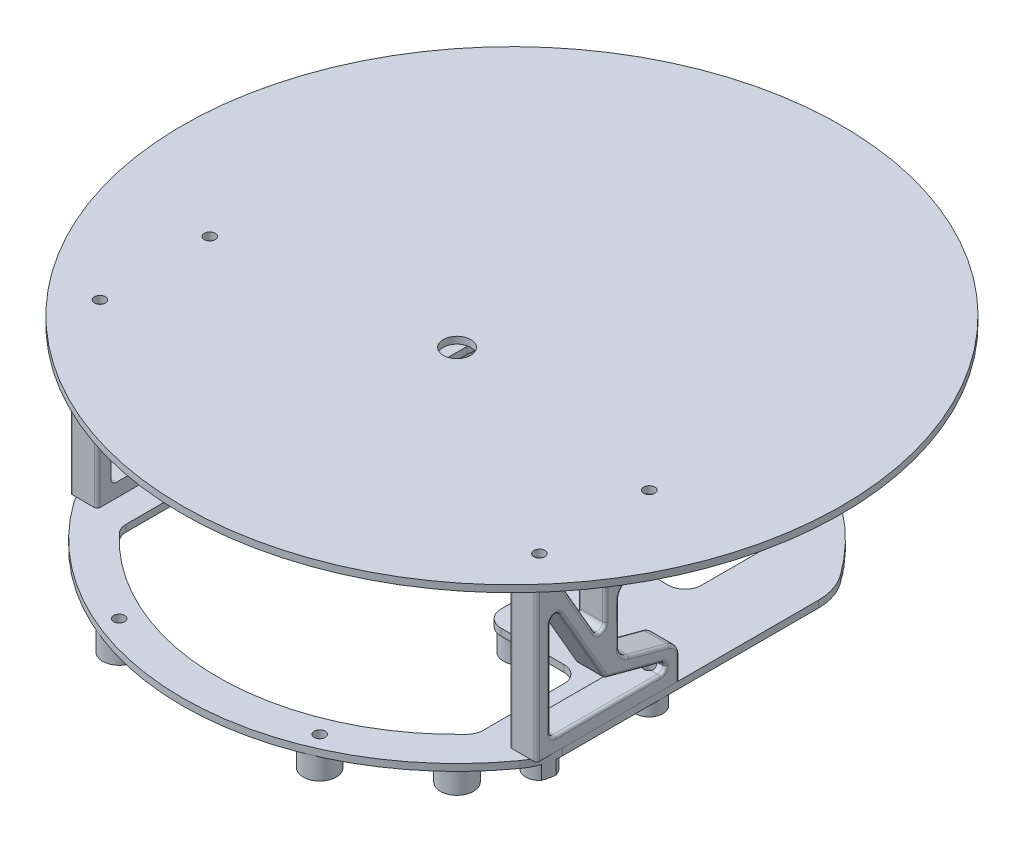
SolidWorks part; units mm, degrees
ref_plane "Front" through (0, 0, 0) normal (0, 0, 1) x (1, 0, 0)
ref_plane "Top" through (0, 0, 0) normal (0, 1, 0) x (1, 0, 0)
ref_plane "Right" through (0, 0, 0) normal (1, 0, 0) x (0, 0, -1)
sketch "Sketch1" plane through (0, 0, 0) normal (0, 1, 0) x (1, 0, 0)
  line L0 (0, 71.1393) -> (0, -87.7098) construction
  line L1 (-42.5, 26.3391) -> (-42.5, -26.3391)
  line L2 (42.5, 26.3391) -> (42.5, -26.3391)
  arc A0 (-42.5, -26.3391) -> (42.5, -26.3391) centre (0, 0) ccw
  arc A1 (42.5, 26.3391) -> (-42.5, 26.3391) centre (0, 0) ccw
  dimension "D1" = 100
  dimension "D2" = 85
extrude "Boss-Extrude1" add sketch "Sketch1" along normal blind 1.25
sketch "Sketch2" plane through (0, 0, 0) normal (0, -1, 0) x (1, 0, 0)
  line L0 (0, 45.5144) -> (0, -63.1722) construction
  line L1 (-51.2989, 0) -> (55.2567, 0) construction
  circle A0 centre (-33, 33) radius 3
  circle A2 centre (-33, 33) radius 1.125
  circle A4 centre (-33, -33) radius 1.125
  circle A5 centre (-33, -33) radius 3
  circle A6 centre (33, -33) radius 3
  circle A7 centre (33, -33) radius 1.125
  circle A8 centre (33, 33) radius 1.125
  circle A9 centre (33, 33) radius 3
  dimension "D3" = 2.25
  dimension "D4" = 6
  dimension "D1" = 66
  dimension "D2" = 66
extrude "Boss-Extrude2" add sketch "Sketch2" along normal blind 4
fillet "Fillet1" radius 10 4 edges at (-42.5, 0.625, -26.3391) (-42.5, 0.625, 26.3391) (42.5, 0.625, -26.3391) (42.5, 0.625, 26.3391)
sketch "Sketch3" plane through (0, 1.25, 0) normal (0, 1, 0) x (1, 0, 0)
  line L0 (0, 58.0627) -> (0, -62.1815) construction
  line L1 (-18.25, -6.75) -> (18.25, -6.75) construction
  line L2 (-18.25, -6.75) -> (-18.25, -43.25) construction
  line L3 (-18.25, -43.25) -> (18.25, -43.25) construction
  line L4 (18.25, -6.75) -> (18.25, -43.25) construction
  line L5 (-18.25, -6.75) -> (18.25, -43.25) construction
  line L6 (-18.25, -43.25) -> (18.25, -6.75) construction
  circle A0 centre (-18.25, -6.75) radius 1
  circle A1 centre (18.25, -6.75) radius 1
  circle A2 centre (18.25, -43.25) radius 1
  circle A3 centre (-18.25, -43.25) radius 1
  circle A4 centre (-40, -5) radius 1
  circle A5 centre (-40, -25) radius 1
  circle A6 centre (40, -25) radius 1
  circle A7 centre (40, -5) radius 1
  point P0 (0, -25)
  dimension "D1" = 2
  dimension "D2" = 36.5
  dimension "D3" = 25
  dimension "D4" = 20
  dimension "D5" = 80
  dimension "D6" = 0
sketch "Sketch4" plane through (0, 0, 0) normal (0, -1, 0) x (1, 0, 0)
  circle A0 centre (-18.25, 43.25) radius 3
  circle A1 centre (18.25, 43.25) radius 3
  circle A2 centre (18.25, 6.75) radius 3
  circle A3 centre (-18.25, 6.75) radius 3
  circle A4 centre (-40, 25) radius 2.5
  circle A5 centre (-40, 5) radius 2.5
  circle A6 centre (40, 25) radius 2.5
  circle A7 centre (40, 5) radius 2.5
  arc M10 (42.5, 23.3184) -> (40.625, 29.1481) centre (32.5, 23.3184) ccw
  arc M16 (-40.625, 29.1481) -> (-42.5, 23.3184) centre (-32.5, 23.3184) ccw
  dimension "D1" = 6
  dimension "D2" = 5
extrude "Boss-Extrude3" add sketch "Sketch4" along normal up to surface (4 mm away) contours A3 | A0 | A1 | A2 region at (-18.25, 0, 43.25) region at (18.25, 0, 43.25) region at (18.25, 0, 6.75) region at (-18.25, 0, 6.75) up to face at (-33, -4, 30)
extrude "Boss-Extrude7" add sketch "Sketch4<3>" along normal offset from surface (2.5 mm away) 1.5 contours A4 M16 | A6 M10 | A5 | A7 region at (-39.9675, 0, 24.9927) region at (39.9675, 0, 24.9927) up to face at (18.25, -4, 3.75)
sketch "Sketch4<3>" plane through (0, 0, 0) normal (0, -1, 0) x (1, 0, 0) same geometry as "Sketch4"
extrude "Cut-Extrude1" cut sketch "Sketch3" against normal through all
sketch "Sketch6" plane through (0, 0, 0) normal (0, -1, 0) x (1, 0, 0)
  line L0 (-29.5, -32.6458) -> (-29.5, -12)
  line L1 (-29.5, -12) -> (-6, -12)
  line L2 (29.5, -12) -> (29.5, -32.6458)
  line L3 (0, 0) -> (0, -57.2909) construction
  line L4 (-32.5, 28.9137) -> (-32.5, 10)
  line L5 (-32.5, 10) -> (-15, 10)
  line L6 (32.5, 10) -> (32.5, 28.9137)
  line L7 (-6, -12) -> (-6, -43.589)
  line L8 (6, -12) -> (6, -43.589)
  line L9 (6, -12) -> (29.5, -12)
  line L10 (15, 10) -> (32.5, 10)
  line L12 (-15, 10) -> (-15, 2)
  line L13 (-15, 2) -> (15, 2)
  line L14 (15, 10) -> (15, 2)
  arc A0 (-29.5, -32.6458) -> (-6, -43.589) centre (0, 0) ccw
  arc A1 (-40.625, -29.1481) -> (40.625, -29.1481) centre (0, 0) ccw construction
  arc A2 (-32.5, 28.9137) -> (32.5, 28.9137) centre (0, 0) cw
  arc A3 (40.625, 29.1481) -> (-40.625, 29.1481) centre (0, 0) ccw construction
  arc A4 (6, -43.589) -> (29.5, -32.6458) centre (0, 0) ccw
  dimension "D2" = 6
  dimension "D4" = 6.5
  dimension "D1" = 59
  dimension "D3" = 12
  dimension "D5" = 10
  dimension "D6" = 12
  dimension "D7" = 65
  dimension "D8" = 8
  dimension "D9" = 30
extrude "Cut-Extrude2" cut sketch "Sketch6" against normal through all
fillet "Fillet2" radius 3 16 edges at (-29.5, 0.625, -12) (-6, 0.625, -12) (-6, 0.625, -43.589) (29.5, 0.625, -12) (29.5, 0.625, -32.6458) (6, 0.625, -43.589) (6, 0.625, -12) (-29.5, 0.625, -32.6458) (32.5, 0.625, 28.9137) (-32.5, 0.625, 28.9137) (-32.5, 0.625, 10) (32.5, 0.625, 10) (15, 0.625, 2) (15, 0.625, 10) (-15, 0.625, 2) (-15, 0.625, 10)
ref_point "Point1"
ref_plane "Plane1" through (-40, 0, 0) normal (-1, 0, 0) x (0, 0, 1)
sketch "Sketch7" plane through (-40, 0, 0) normal (-1, 0, 0) x (0, 0, 1)
  line L0 (2, 1.25) -> (2, 7.25)
  line L1 (-23.3184, 1.25) -> (23.3184, 1.25) construction
  line L2 (2, 7.25) -> (13, 10.1974)
  line L3 (13, 10.1974) -> (13, 21.3026)
  line L4 (13, 21.3026) -> (2, 24.25)
  line L5 (2, 24.25) -> (2, 30.25)
  line L6 (2, 30.25) -> (28, 30.25)
  line L7 (28, 30.25) -> (28, 1.25)
  line L8 (28, 1.25) -> (2, 1.25)
  line L9 (4.5, 27.75) -> (23.8548, 27.75)
  line L11 (25.5, 3.75) -> (4.5, 3.75)
  line L12 (4.5, 3.75) -> (4.5, 5.3317)
  line L13 (4.5, 5.3317) -> (15.5, 8.2791)
  line L14 (15.5, 13.2791) -> (15.5, 23.2209)
  line L15 (15.5, 23.2209) -> (4.5, 26.1683)
  line L16 (4.5, 26.1683) -> (4.5, 27.75)
  line L17 (15.5, 8.2791) -> (25.5, 25.5996)
  line L19 (23.8548, 27.75) -> (15.5, 13.2791)
  line L21 (15.5, 8.2791) -> (15.5, 23.2209) construction
  line L22 (25.5, 25.5996) -> (25.5, 3.75)
  line L23 (25.5, 27.75) -> (25.5, 3.75) construction
  line L24 (4.5, 27.75) -> (25.5, 27.75) construction
  dimension "D1" = 2
  dimension "D2" = 26
  dimension "D3" = 15
  dimension "D4" = 15
  dimension "D5" = 15
  dimension "D6" = 6
  dimension "D7" = 29
  dimension "D9" = 2.5
  dimension "D10" = 30
  dimension "D8" = 2.5
extrude "Boss-Extrude4" add sketch "Sketch7" along normal mid plane 5 separate body
fillet "Fillet3" radius 2.5 4 edges at (-40, 7.25, 2) (-40, 10.1974, 13) (-40, 21.3026, 13) (-40, 24.25, 2)
fillet "Fillet4" radius 1 10 edges at (-40, 25.5996, 25.5) (-40, 8.2791, 15.5) (-40, 5.3317, 4.5) (-40, 3.75, 25.5) (-40, 3.75, 4.5) (-40, 13.2791, 15.5) (-40, 27.75, 4.5) (-40, 26.1683, 4.5) (-40, 23.2209, 15.5) (-40, 27.75, 23.8548)
fillet "Fillet5" radius 0.5 47 edges at (-37.5, 15.75, 28) (-37.5, 3.2908, 2) (-37.5, 6.8536, 2.5166) (-37.5, 8.7237, 7.5) (-37.5, 10.5939, 12.4834) (-37.5, 15.75, 13) (-37.5, 20.9061, 12.4834) (-37.5, 22.7763, 7.5) (-37.5, 24.6464, 2.5166) (-37.5, 28.2092, 2) (-42.5, 3.2908, 2) (-42.5, 6.8536, 2.5166) (-42.5, 8.7237, 7.5) (-42.5, 10.5939, 12.4834) (-42.5, 15.75, 13) (-42.5, 20.9061, 12.4834) (-42.5, 22.7763, 7.5) (-42.5, 24.6464, 2.5166) (-42.5, 28.2092, 2) (-42.5, 15.75, 28) (-42.5, 4.0108, 4.8265) (-42.5, 5.2093, 4.7358) (-42.5, 6.8511, 10.1705) (-42.5, 8.3445, 15.4498) (-42.5, 15.5027, 19.6705) (-42.5, 22.8335, 24.7588) (-42.5, 13.3088, 25.5) (-42.5, 4.0429, 25.2071) (-42.5, 3.75, 15) (-37.5, 27.4892, 4.8265) (-42.5, 27.4892, 4.8265) (-37.5, 26.2907, 4.7358) (-37.5, 24.6946, 10) (-37.5, 23.0623, 15.2934) (-37.5, 19.7324, 15.5) (-37.5, 16.0452, 16.2412) (-42.5, 26.2907, 4.7358) (-42.5, 24.6946, 10) (-42.5, 23.0623, 15.2934) (-42.5, 19.7324, 15.5) (-42.5, 16.0452, 16.2412) (-37.5, 27.75, 13.8114) (-42.5, 27.75, 13.8114) (-37.5, 21.3806, 20.1774) (-42.5, 21.3806, 20.1774) (-37.5, 27.25, 22.9887) (-42.5, 27.25, 22.9887)
sketch "Sketch8" plane through (0, 1.25, 0) normal (0, -1, 0) x (1, 0, 0)
  circle A2 centre (-40, 5) radius 1
  circle A3 centre (-40, 25) radius 1
extrude "Cut-Extrude3" cut sketch "Sketch8" against normal blind 3.5
extrude "Cut-Extrude4" cut sketch "Sketch8<3>" along normal blind 3.5 from surface starting at face at (-40, 30.25, 15)
sketch "Sketch8<3>" plane through (0, 1.25, 0) normal (0, -1, 0) x (1, 0, 0) same geometry as "Sketch8"
mirror "Mirror1" about plane through (0, 0, 0) normal (1, 0, 0) of bodies 109
sketch "Sketch9" plane through (0, 30.25, 0) normal (0, 1, 0) x (1, 0, 0)
  line L0 (-42.5, 23.3184) -> (-42.5, -23.3184) construction
  line L1 (42.5, -23.3184) -> (42.5, 23.3184) construction
  line L2 (-42.5, 23.3184) -> (-42.5, -23.3184) construction
  line L3 (42.5, -23.3184) -> (42.5, 23.3184) construction
  arc A0 (40.625, 29.1481) -> (-40.625, 29.1481) centre (0, 0) ccw construction
  arc A1 (-40.625, 29.1481) -> (-42.5, 23.3184) centre (-32.5, 23.3184) ccw construction
  arc A2 (-42.5, -23.3184) -> (-40.625, -29.1481) centre (-32.5, -23.3184) ccw construction
  arc A3 (-40.625, -29.1481) -> (40.625, -29.1481) centre (0, 0) ccw construction
  arc A4 (40.625, -29.1481) -> (42.5, -23.3184) centre (32.5, -23.3184) ccw construction
  arc A5 (42.5, 23.3184) -> (40.625, 29.1481) centre (32.5, 23.3184) ccw construction
  arc A6 (-40.625, 29.1481) -> (-42.5, 23.3184) centre (-32.5, 23.3184) ccw construction
  arc A7 (-42.5, -23.3184) -> (-40.625, -29.1481) centre (-32.5, -23.3184) ccw construction
  arc A8 (-40.625, -29.1481) -> (40.625, -29.1481) centre (0, 0) ccw construction
  arc A9 (40.625, -29.1481) -> (42.5, -23.3184) centre (32.5, -23.3184) ccw construction
  arc A10 (42.5, 23.3184) -> (40.625, 29.1481) centre (32.5, 23.3184) ccw construction
  arc A11 (40.625, 29.1481) -> (-40.625, 29.1481) centre (0, 0) ccw construction
  circle A14 centre (0, 10) radius 60
  dimension "D1" = 120
  dimension "D2" = 10
extrude "Boss-Extrude6" add sketch "Sketch9" along normal blind 1.25 separate body
sketch "Sketch12" plane through (0, 31.5, 0) normal (0, 1, 0) x (1, 0, 0)
  circle A0 centre (40, -5) radius 1 construction
  circle A1 centre (40, -25) radius 1 construction
  circle A2 centre (-40, -5) radius 1 construction
  circle A3 centre (-40, -25) radius 1 construction
  circle A4 centre (40, -5) radius 1
  circle A5 centre (40, -25) radius 1
  circle A6 centre (-40, -5) radius 1
  circle A7 centre (-40, -25) radius 1
  circle A8 centre (0, 0) radius 2.5
  dimension "D1" = 5
extrude "Cut-Extrude7" cut sketch "Sketch12" against normal up to next (1.25 mm away)
equation "\"D5@Sketch7\"=\"D4@Sketch7\""
